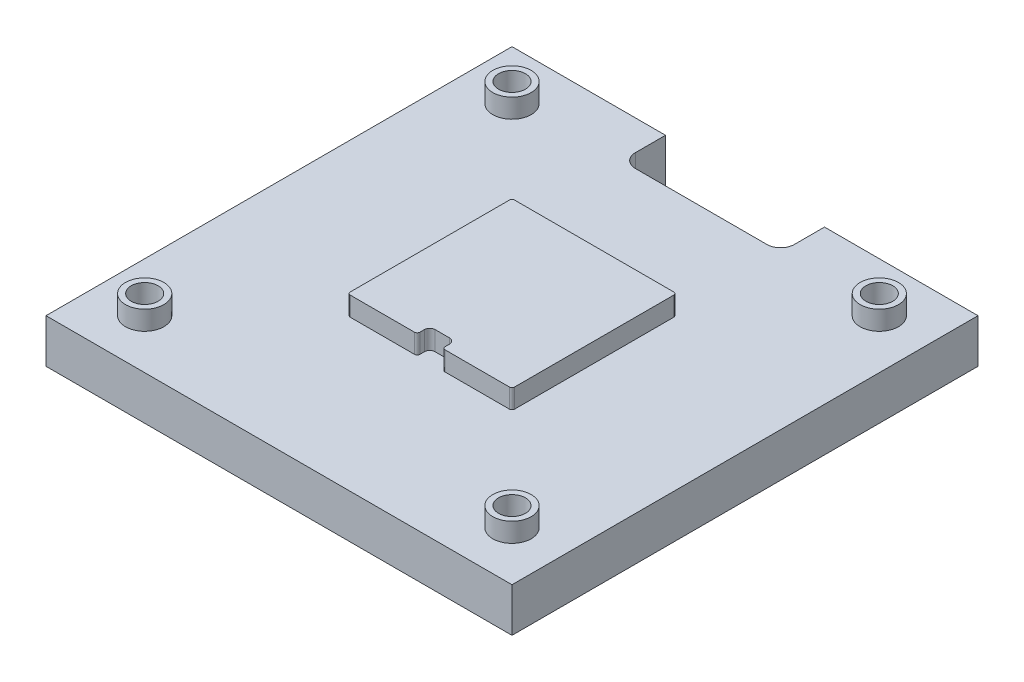
SolidWorks part; units mm, degrees
material "Copper"
ref_plane "Front Plane" through (0, 0, 0) normal (0, 0, 1) x (1, 0, 0)
ref_plane "Top Plane" through (0, 0, 0) normal (0, 1, 0) x (1, 0, 0)
ref_plane "Right Plane" through (0, 0, 0) normal (1, 0, 0) x (0, 0, -1)
sketch "Sketch1" plane through (0, 0, 0) normal (0, 1, 0) x (1, 0, 0)
  line L0 (-71.3469, 0) -> (71.3469, 0) construction
  line L1 (-42.5, 42.5) -> (42.5, 42.5)
  line L2 (-42.5, 42.5) -> (-42.5, -42.5)
  line L3 (-42.5, -42.5) -> (42.5, -42.5)
  line L4 (42.5, 42.5) -> (42.5, -42.5)
  line L5 (-42.5, 42.5) -> (42.5, -42.5) construction
  line L6 (-42.5, -42.5) -> (42.5, 42.5) construction
  line L7 (0, -59.0713) -> (0, 59.0713) construction
  circle A0 centre (-33.5, 33.5) radius 2.4575
  circle A1 centre (-33.5, -33.5) radius 2.4575
  circle A2 centre (33.5, -33.5) radius 2.4575
  circle A3 centre (33.5, 33.5) radius 2.4575
  point P0 (0, 0)
  dimension "D3" = 4.915
  dimension "D1" = 85
  dimension "D2" = 85
  dimension "D4" = 9
  dimension "D5" = 9
extrude "Boss-Extrude1" add sketch "Sketch1" along normal blind 8
sketch "Sketch2" plane through (0, 0, 0) normal (0, -1, 0) x (1, 0, 0)
  line L0 (0, -4.4) -> (0, 4.4) construction
  line L1 (4.4, 0) -> (-4.4, 0) construction
  circle A0 centre (-33.5, 33.5) radius 3.969
  circle A1 centre (33.5, 33.5) radius 3.969
  circle A2 centre (33.5, -33.5) radius 3.969
  circle A3 centre (-33.5, -33.5) radius 3.969
  dimension "D1" = 7.938
extrude "Cut-Extrude1" cut sketch "Sketch2" against normal blind 4.166
sketch "Sketch3" plane through (0, 8, 0) normal (0, 1, 0) x (1, 0, 0)
  line L0 (0, -4.4) -> (0, 4.4) construction
  line L1 (-4.4, 0) -> (4.4, 0) construction
  circle A0 centre (33.5, -33.5) radius 3.5
  circle A1 centre (33.5, -33.5) radius 2.4575
  circle A2 centre (33.5, -33.5) radius 2.4575 construction
  circle A3 centre (-33.5, -33.5) radius 2.4575
  circle A4 centre (-33.5, -33.5) radius 3.5
  circle A5 centre (-33.5, 33.5) radius 3.5
  circle A6 centre (-33.5, 33.5) radius 2.4575
  circle A7 centre (33.5, 33.5) radius 2.4575
  circle A8 centre (33.5, 33.5) radius 3.5
  dimension "D1" = 7
extrude "Boss-Extrude2" add sketch "Sketch3" along normal blind 3.5
sketch "Sketch4" plane through (0, 8, 0) normal (0, 1, 0) x (1, 0, 0)
  line L0 (2.2929, -14.5) -> (2.2929, -13.7071)
  line L1 (14.5, -15) -> (2.7929, -15)
  line L2 (15, -14.5) -> (15, 14.5)
  line L3 (14.5, 15) -> (-14.5, 15)
  line L4 (-15, -14.5) -> (-15, 14.5)
  line L5 (15, -15) -> (-15, 15) construction
  line L6 (15, 15) -> (-15, -15) construction
  line L7 (1.2929, -12.7071) -> (-1.2929, -12.7071)
  line L8 (-2.2929, -13.7071) -> (-2.2929, -14.5)
  line L9 (-2.7929, -15) -> (-14.5, -15)
  arc A0 (-14.5, 15) -> (-15, 14.5) centre (-14.5, 14.5) ccw
  arc A1 (15, 14.5) -> (14.5, 15) centre (14.5, 14.5) ccw
  arc A2 (-14.5, -15) -> (-15, -14.5) centre (-14.5, -14.5) cw
  arc A3 (14.5, -15) -> (15, -14.5) centre (14.5, -14.5) ccw
  arc A4 (-2.2929, -14.5) -> (-2.7929, -15) centre (-2.7929, -14.5) cw
  arc A5 (2.2929, -14.5) -> (2.7929, -15) centre (2.7929, -14.5) ccw
  arc A6 (-1.2929, -12.7071) -> (-2.2929, -13.7071) centre (-1.2929, -13.7071) ccw
  arc A7 (2.2929, -13.7071) -> (1.2929, -12.7071) centre (1.2929, -13.7071) ccw
  point P0 (0, 0)
  point P10 (0, -12.7071)
  point P25 (-2.2929, -15)
  point P30 (-2.2929, -12.7071)
  point P33 (2.2929, -12.7071)
  dimension "D4" = 0.5
  dimension "D6" = 0.5
  dimension "D7" = 1
  dimension "D1" = 30
  dimension "D2" = 2.2929
  dimension "D3" = 4.5858
  dimension "D5" = 30
extrude "Boss-Extrude3" add sketch "Sketch4" along normal blind 3.5
sketch "Sketch5" plane through (0, 8, 0) normal (0, 1, 0) x (1, 0, 0)
  line L0 (42.5, 42.5) -> (-42.5, 42.5) construction
  line L1 (14.5, 42.5) -> (-14.5, 42.5)
  line L2 (14.5, 42.5) -> (14.5, 34.5)
  line L3 (14.5, 34.5) -> (-14.5, 34.5)
  line L4 (-14.5, 42.5) -> (-14.5, 34.5)
  point P6 (0, 34.5)
  dimension "D1" = 29
  dimension "D2" = 8
extrude "Cut-Extrude2" cut sketch "Sketch5" against normal blind 10
fillet "Fillet1" radius 2.5 2 edges at (-14.5, 4, -34.5) (14.5, 4, -34.5)
